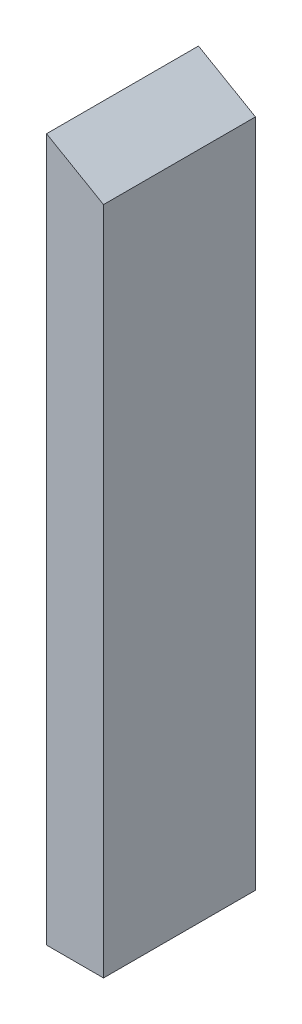
SolidWorks part; units mm, degrees
ref_plane "Front Plane" through (0, 0, 0) normal (0, 0, 1) x (1, 0, 0)
ref_plane "Top Plane" through (0, 0, 0) normal (0, 1, 0) x (1, 0, 0)
ref_plane "Right Plane" through (0, 0, 0) normal (1, 0, 0) x (0, 0, -1)
sketch "Sketch1" plane through (0, 0, 0) normal (0, 0, 1) x (1, 0, 0)
  line L0 (-19.4361, 59.5794) -> (-16.4361, 57.8473)
  line L2 (-19.4361, 59.5794) -> (-19.4361, 22.5794)
  line L3 (-19.4361, 22.5794) -> (-16.4361, 22.5794)
  line L4 (-16.4361, 57.8473) -> (-16.4361, 22.5794)
  dimension "D1" = 37
  dimension "D2" = 3
  dimension "D3" = 60
extrude "Boss-Extrude1" add sketch "Sketch1" along normal blind 8
